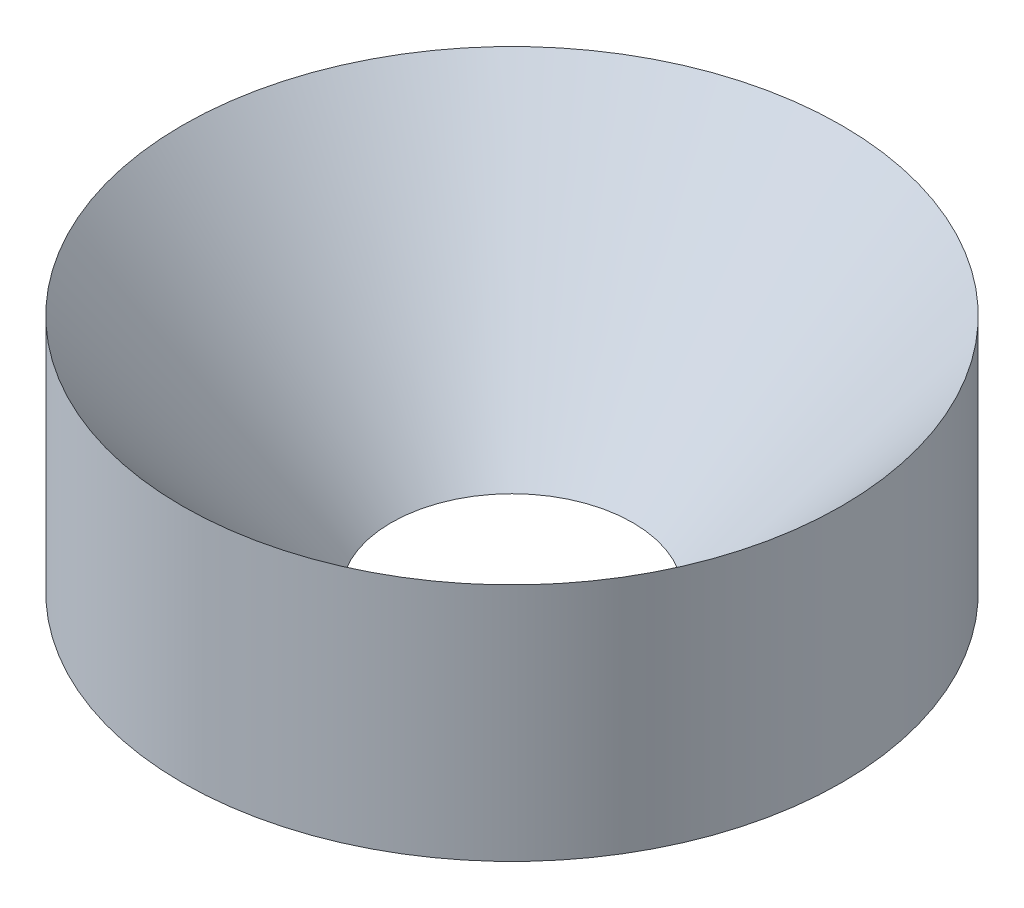
SolidWorks part; units mm, degrees
ref_plane "Piano frontale" through (0, 0, 0) normal (0, 0, 1) x (1, 0, 0)
ref_plane "Piano superiore" through (0, 0, 0) normal (0, 1, 0) x (1, 0, 0)
ref_plane "Piano destro" through (0, 0, 0) normal (1, 0, 0) x (0, 0, -1)
sketch "Schizzo1" plane through (0, 0, 0) normal (0, 0, 1) x (1, 0, 0)
  line L0 (-71, 51.5845) -> (-71, 0)
  line L1 (-71, 0) -> (-26, 0)
  line L2 (-26, 0) -> (-71, 51.5845)
  line L3 (0, 0) -> (0, 150.3289) construction
  point P6 (0, 0)
  dimension "D1" = 45
  dimension "D2" = 48.9
  dimension "D3" = 52
revolve "Rivoluzione1" add sketch "Schizzo1" angle 360 about L3
